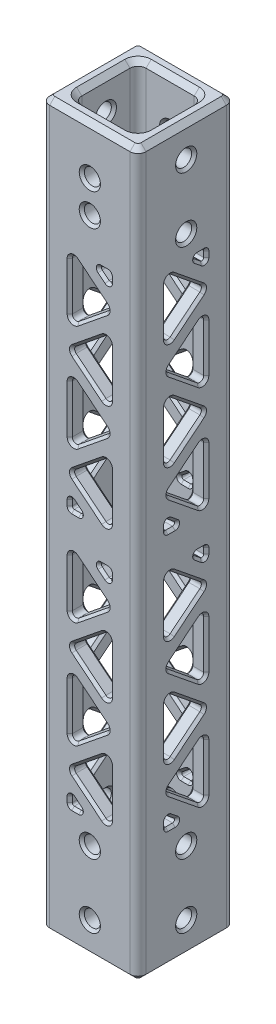
SolidWorks part; units mm, degrees
note: '?' marks a value the reader was unsure of.
ref_plane "Front Plane" through (0, 0, 0) normal (0, 0, 1) x (1, 0, 0)
ref_plane "Top Plane" through (0, 0, 0) normal (0, 1, 0) x (1, 0, 0)
ref_plane "Right Plane" through (0, 0, 0) normal (1, 0, 0) x (0, 0, -1)
sketch "Sketch1" plane through (0, 0, 0) normal (0, 1, 0) x (1, 0, 0)
  line L1 (-9.525, -9.525) -> (9.525, -9.525)
  line L2 (-9.525, -9.525) -> (-9.525, 9.525)
  line L3 (-9.525, 9.525) -> (9.525, 9.525)
  line L4 (9.525, -9.525) -> (9.525, 9.525)
  line L5 (-9.525, -9.525) -> (9.525, 9.525) construction
  line L6 (-9.525, 9.525) -> (9.525, -9.525) construction
  line L7 (-6.35, -6.35) -> (6.35, -6.35)
  line L8 (-6.35, -6.35) -> (-6.35, 6.35)
  line L9 (-6.35, 6.35) -> (6.35, 6.35)
  line L10 (6.35, -6.35) -> (6.35, 6.35)
  line L11 (-6.35, -6.35) -> (6.35, 6.35) construction
  line L12 (-6.35, 6.35) -> (6.35, -6.35) construction
  point P0 (0, 0)
  point P6 (0, 0)
  dimension "D1" = 19.05
  dimension "D2" = 19.05
  dimension "D3" = 12.7
extrude "Boss-Extrude1" add sketch "Sketch1" along normal mid plane 142.875 contours L3 L4 L1 L2
hole_wizard "1/8 (0.125) Diameter Hole1" positions "Sketch8" profile "Sketch9" hole size "1/8" standard "ANSI Inch" end condition through all
sketch "Sketch8" plane through (-9.525, 0, 0) normal (-1, 0, 0) x (0, 0, 1)
  line L2 (0, 65.0875) -> (0, 71.4375) construction
  line L3 (-9.525, 71.4375) -> (9.525, 71.4375) construction
  point P0 (0, 65.0875)
  point P2 (0, 52.3875)
  dimension "D1" = 12.7
  dimension "D2" = 6.35
sketch "Sketch9" plane through (-9.525, 65.0875, 0) normal (0, 1, 0) x (0, 0, 1)
  line L0 (0, 0) -> (0, 19.05)
  line L1 (0, 19.05) -> (1.5875, 19.05)
  line L2 (1.5875, 19.05) -> (1.5875, 0)
  line L5 (1.5875, 0) -> (0, 0)
  line L11 (0, -6.35) -> (0, 107.95) construction
  dimension "Thru Hole Dia." = 3.175
  dimension "Thru Hole Depth" = 19.05
hole_wizard "1/8 (0.125) Diameter Hole2" positions "Sketch10" profile "Sketch11" hole size "1/8" standard "ANSI Inch" end condition through all
sketch "Sketch10" plane through (9.525, 0, 0) normal (1, 0, 0) x (0, 0, -1)
  line L0 (0, -71.4375) -> (0, -65.0875) construction
  line L1 (-9.525, -71.4375) -> (9.525, -71.4375) construction
  point P0 (0, -52.3875)
  point P2 (0, -65.0875)
  dimension "D1" = 12.7
  dimension "D2" = 6.35
sketch "Sketch11" plane through (9.525, -52.3875, 0) normal (0, 1, 0) x (0, 0, -1)
  line L0 (0, 0) -> (0, 19.05)
  line L1 (0, 19.05) -> (1.5875, 19.05)
  line L2 (1.5875, 19.05) -> (1.5875, 0)
  line L5 (1.5875, 0) -> (0, 0)
  line L11 (0, -6.35) -> (0, 107.95) construction
  dimension "Thru Hole Dia." = 3.175
  dimension "Thru Hole Depth" = 19.05
hole_wizard "1/8 (0.125) Diameter Hole3" positions "Sketch15" profile "Sketch16" hole size "1/8" standard "ANSI Inch" end condition through all
sketch "Sketch15" plane through (0, 0, 9.525) normal (0, 0, 1) x (1, 0, 0)
  line L4 (0, -71.4375) -> (0, -65.0875) construction
  line L5 (-9.525, -71.4375) -> (9.525, -71.4375) construction
  line L6 (0, -65.0875) -> (0, -52.3875) construction
  line L7 (0, 55.5625) -> (0, 61.9125) construction
  line L11 (0, 61.9125) -> (0, 71.4375) construction
  line L12 (-9.525, 71.4375) -> (9.525, 71.4375) construction
  point P0 (0, 61.9125)
  point P2 (0, 55.5625)
  point P14 (0, -65.0875)
  point P16 (0, -52.3875)
  dimension "D1" = 6.35
  dimension "D2" = 9.525
  dimension "D3" = 6.35
  dimension "D4" = 12.7
sketch "Sketch16" plane through (0, 61.9125, 9.525) normal (1, 0, 0) x (0, -1, 0)
  line L0 (0, 0) -> (0, 19.05)
  line L1 (0, 19.05) -> (1.5875, 19.05)
  line L2 (1.5875, 19.05) -> (1.5875, 0)
  line L5 (1.5875, 0) -> (0, 0)
  line L11 (0, -6.35) -> (0, 107.95) construction
  dimension "Thru Hole Dia." = 3.175
  dimension "Thru Hole Depth" = 19.05
sketch "Sketch14" plane through (0, 0, 0) normal (1, 0, 0) x (0, 0, -1)
  line L0 (-3.9688, 47.625) -> (3.9688, 47.625) construction
  line L3 (3.9688, 47.625) -> (3.9688, -47.625) construction
  line L4 (-3.9688, -30.6626) -> (3.9688, -24.2253)
  line L5 (3.9688, -24.2253) -> (3.9688, -37.0998)
  line L6 (3.9688, -47.625) -> (-3.9688, -47.625) construction
  line L9 (-3.9688, -47.625) -> (-3.9688, 47.625) construction
  line L10 (0, 53.975) -> (0, 47.625) construction
  line L11 (0, -53.975) -> (0, -47.625) construction
  line L12 (-3.9687, 3.175) -> (3.9687, 3.175) construction
  line L13 (-3.9687, -3.175) -> (3.9687, -3.175) construction
  line L14 (0, -3.175) -> (0, 3.175) construction
  line L15 (-3.9688, 47.625) -> (-1.0718, 47.625)
  line L16 (-1.0718, 47.625) -> (-3.9688, 45.2756)
  line L17 (-3.9688, 45.2756) -> (-3.9688, 47.625)
  line L18 (3.9688, 47.625) -> (-3.9688, 41.1877)
  line L19 (-3.9688, 41.1877) -> (3.9688, 34.7505)
  line L20 (3.9688, 34.7505) -> (3.9688, 47.625)
  line L21 (0, 44.4064) -> (-1.9999, 46.8723) construction
  line L22 (-3.9688, 37.0998) -> (3.9688, 30.6626)
  line L23 (3.9688, 30.6626) -> (-3.9688, 24.2253)
  line L24 (-3.9688, 24.2253) -> (-3.9688, 37.0998)
  line L25 (0, 37.9691) -> (-1.9999, 35.5031) construction
  line L26 (3.9688, 26.5747) -> (-3.9688, 20.1374)
  line L27 (-3.9688, 20.1374) -> (3.9688, 13.7002)
  line L28 (3.9688, 13.7002) -> (3.9688, 26.5747)
  line L29 (-3.9687, 3.175) -> (3.9688, 9.6123)
  line L30 (3.9688, 9.6123) -> (-3.9688, 16.0495)
  line L31 (-3.9688, 16.0495) -> (-3.9687, 3.175)
  line L32 (0, 23.3561) -> (-1.9999, 25.822) construction
  line L33 (1.0718, 3.175) -> (3.9687, 3.175)
  line L34 (3.9687, 3.175) -> (3.9688, 5.5244)
  line L35 (3.9688, 5.5244) -> (1.0718, 3.175)
  line L36 (0, 16.9188) -> (-1.9999, 14.4528) construction
  line L37 (0, 6.3936) -> (1.9999, 3.9277) construction
  line L38 (-1.0718, -3.175) -> (-3.9687, -3.175)
  line L39 (-3.9687, -3.175) -> (-3.9688, -5.5244)
  line L40 (-3.9688, -5.5244) -> (-1.0718, -3.175)
  line L41 (3.9687, -3.175) -> (-3.9688, -9.6123)
  line L42 (-3.9688, -9.6123) -> (3.9688, -16.0495)
  line L43 (3.9688, -16.0495) -> (3.9687, -3.175)
  line L44 (0, -6.3936) -> (-1.9999, -3.9277) construction
  line L45 (-3.9688, -13.7002) -> (3.9688, -20.1374)
  line L46 (3.9688, -20.1374) -> (-3.9688, -26.5747)
  line L47 (-3.9688, -26.5747) -> (-3.9688, -13.7002)
  line L48 (0, -16.9188) -> (1.9999, -14.4528) construction
  line L49 (3.9688, -37.0998) -> (-3.9688, -30.6626)
  line L50 (-3.9688, -47.625) -> (3.9688, -41.1877)
  line L51 (3.9688, -41.1877) -> (-3.9688, -34.7505)
  line L52 (-3.9688, -34.7505) -> (-3.9688, -47.625)
  line L53 (0, -27.4439) -> (-1.9999, -24.978) construction
  line L54 (0, -37.9691) -> (1.9999, -35.5031) construction
  line L55 (1.0718, -47.625) -> (3.9688, -47.625)
  line L56 (3.9688, -47.625) -> (3.9688, -45.2756)
  line L57 (3.9688, -45.2756) -> (1.0718, -47.625)
  line L58 (2.5203, -46.4503) -> (0.5204, -43.9843) construction
  circle A6 centre (0, 52.3875) radius 1.5875 construction
  circle A7 centre (0, -52.3875) radius 1.5875 construction
  dimension "D3" = 3.175
  dimension "D1" = 6.35
  dimension "D2" = 7.9375
extrude "Cut-Extrude1" cut sketch "Sketch14" against normal up to next
ref_axis "Axis1" through (0, -78.5813, 0) along (0, 1, 0)?
pattern_circular "CirPattern1" count 4 over 360 about axis through (0, 0, 0) along (0, 1, 0) of "Cut-Extrude1"
fillet "Fillet1" radius 1.5875 8 edges at (9.525, 0, -9.525) (9.525, 0, 9.525) (-9.525, 0, -9.525) (-9.525, 0, 9.525) (6.35, 0, -6.35) (6.35, 0, 6.35) (-6.35, 0, 6.35) (-6.35, 0, -6.35)
fillet "Fillet2" radius 0.7937 96 edges at (-3.9688, 41.1877, -7.9375) (3.9687, 47.625, -7.9375) (3.9687, 34.7505, -7.9375) (3.9687, 30.6626, -7.9375) (-3.9688, 37.0998, -7.9375) (-3.9688, 24.2253, -7.9375) (-3.9688, 20.1374, -7.9375) (3.9687, 26.5747, -7.9375) (3.9687, 13.7002, -7.9375) (3.9687, 9.6123, -7.9375) (-3.9688, 16.0495, -7.9375) (-3.9688, 3.175, -7.9375) (-3.9688, -9.6123, -7.9375) (3.9687, -3.175, -7.9375) (3.9687, -16.0495, -7.9375) (-3.9688, -26.5747, -7.9375) (-3.9688, -13.7002, -7.9375) (3.9687, -20.1374, -7.9375) (3.9687, -24.2253, -7.9375) (-3.9688, -30.6626, -7.9375) (3.9687, -37.0998, -7.9375) (3.9687, -41.1877, -7.9375) (-3.9688, -34.7505, -7.9375) (-3.9688, -47.625, -7.9375) (-7.9375, -47.625, 3.9688) (-7.9375, -34.7505, 3.9688) (-7.9375, -41.1877, -3.9688) (-7.9375, -24.2253, -3.9688) (-7.9375, -30.6626, 3.9688) (-7.9375, -37.0998, -3.9688) (-7.9375, -26.5747, 3.9688) (-7.9375, -13.7002, 3.9688) (-7.9375, -20.1374, -3.9688) (-7.9375, -9.6123, 3.9688) (-7.9375, -3.175, -3.9687) (-7.9375, -16.0495, -3.9687) (-7.9375, 3.175, 3.9687) (-7.9375, 16.0495, 3.9688) (-7.9375, 9.6123, -3.9688) (-7.9375, 20.1374, 3.9688) (-7.9375, 26.5747, -3.9688) (-7.9375, 13.7002, -3.9688) (-7.9375, 24.2253, 3.9688) (-7.9375, 37.0998, 3.9688) (-7.9375, 30.6626, -3.9688) (-7.9375, 41.1877, 3.9687) (-7.9375, 47.625, -3.9688) (-7.9375, 34.7505, -3.9687) (-3.9687, 47.625, 7.9375) (-3.9687, 34.7505, 7.9375) (3.9688, 41.1877, 7.9375) (-3.9687, 30.6626, 7.9375) (3.9688, 24.2253, 7.9375) (3.9688, 37.0998, 7.9375) (-3.9687, 26.5747, 7.9375) (-3.9687, 13.7002, 7.9375) (3.9688, 20.1374, 7.9375) (-3.9687, 9.6123, 7.9375) (3.9688, 16.0495, 7.9375) (3.9688, 3.175, 7.9375) (-3.9687, -3.175, 7.9375) (-3.9687, -16.0495, 7.9375) (3.9688, -9.6123, 7.9375) (-3.9687, -20.1374, 7.9375) (3.9688, -13.7002, 7.9375) (3.9688, -26.5747, 7.9375) (-3.9687, -24.2253, 7.9375) (-3.9687, -37.0998, 7.9375) (3.9688, -30.6626, 7.9375) (-3.9687, -41.1877, 7.9375) (3.9688, -34.7505, 7.9375) (3.9688, -47.625, 7.9375) (7.9375, -41.1877, 3.9688) (7.9375, -34.7505, -3.9688) (7.9375, -47.625, -3.9688) (7.9375, -24.2253, 3.9688) (7.9375, -37.0998, 3.9688) (7.9375, -30.6626, -3.9688) (7.9375, -26.5747, -3.9687) (7.9375, -13.7002, -3.9688) (7.9375, -20.1374, 3.9688) (7.9375, -3.175, 3.9687) (7.9375, -16.0495, 3.9687) (7.9375, -9.6123, -3.9688) (7.9375, 3.175, -3.9687) (7.9375, 16.0495, -3.9688) (7.9375, 9.6123, 3.9688) (7.9375, 26.5747, 3.9688) (7.9375, 13.7002, 3.9688) (7.9375, 20.1374, -3.9688) (7.9375, 24.2253, -3.9688) (7.9375, 37.0998, -3.9688) (7.9375, 30.6626, 3.9688) (7.9375, 41.1877, -3.9688) (7.9375, 34.7505, 3.9687) (7.9375, 47.625, 3.9688)
fillet "Fillet3" radius 0.3969 48 edges at (1.0718, 47.625, 7.9375) (3.9688, 45.2756, 7.9375) (3.9688, 47.625, 7.9375) (-1.0718, 3.175, 7.9375) (-3.9687, 5.5244, 7.9375) (-3.9687, 3.175, 7.9375) (1.0718, -3.175, 7.9375) (3.9688, -5.5244, 7.9375) (3.9688, -3.175, 7.9375) (-1.0718, -47.625, 7.9375) (-3.9687, -45.2756, 7.9375) (-3.9687, -47.625, 7.9375) (7.9375, -47.625, 1.0718) (7.9375, -45.2756, 3.9688) (7.9375, -47.625, 3.9688) (7.9375, -3.175, -1.0718) (7.9375, -3.175, -3.9687) (7.9375, -5.5244, -3.9688) (7.9375, 3.175, 1.0718) (7.9375, 5.5244, 3.9688) (7.9375, 3.175, 3.9687) (7.9375, 47.625, -1.0718) (7.9375, 45.2756, -3.9688) (7.9375, 47.625, -3.9688) (-7.9375, 45.2756, 3.9687) (-7.9375, 47.625, 3.9688) (-7.9375, 47.625, 1.0718) (-7.9375, 3.175, -1.0718) (-7.9375, 5.5244, -3.9688) (-7.9375, 3.175, -3.9687) (-7.9375, -5.5244, 3.9688) (-7.9375, -3.175, 3.9687) (-7.9375, -3.175, 1.0718) (-7.9375, -47.625, -1.0718) (-7.9375, -45.2756, -3.9688) (-7.9375, -47.625, -3.9688) (1.0718, -47.625, -7.9375) (3.9687, -45.2756, -7.9375) (3.9687, -47.625, -7.9375) (-3.9688, -5.5244, -7.9375) (-3.9688, -3.175, -7.9375) (-1.0718, -3.175, -7.9375) (1.0718, 3.175, -7.9375) (3.9687, 5.5244, -7.9375) (3.9687, 3.175, -7.9375) (-3.9688, 45.2756, -7.9375) (-3.9688, 47.625, -7.9375) (-1.0718, 47.625, -7.9375)
chamfer "Chamfer1" distance 1.016 angle 45 32 edges at (9.525, 71.4375, 0) (9.06, 71.4375, -9.06) (9.06, 71.4375, 9.06) (0, 71.4375, -9.525) (0, 71.4375, 9.525) (-9.06, 71.4375, -9.06) (-9.06, 71.4375, 9.06) (-9.525, 71.4375, 0) (6.35, 71.4375, 0) (5.885, 71.4375, -5.885) (5.885, 71.4375, 5.885) (0, 71.4375, -6.35) (0, 71.4375, 6.35) (-5.885, 71.4375, -5.885) (-5.885, 71.4375, 5.885) (-6.35, 71.4375, 0) (0, -71.4375, 9.525) (9.06, -71.4375, 9.06) (-9.06, -71.4375, 9.06) (9.525, -71.4375, 0) (-9.525, -71.4375, 0) (9.06, -71.4375, -9.06) (-9.06, -71.4375, -9.06) (0, -71.4375, -9.525) (0, -71.4375, 6.35) (5.885, -71.4375, 5.885) (-5.885, -71.4375, 5.885) (6.35, -71.4375, 0) (-6.35, -71.4375, 0) (5.885, -71.4375, -5.885) (-5.885, -71.4375, -5.885) (0, -71.4375, -6.35)
chamfer "Chamfer2" distance 0.508 angle 45 608 edges at (2.8816, 47.625, 9.525) (2.8816, 47.625, 6.35) (2.6316, 46.36, 9.525) (2.6316, 46.36, 6.35) (3.9688, 46.6683, 9.525) (3.9688, 46.6683, 6.35) (-2.8816, 3.175, 9.525) (-2.8816, 3.175, 6.35) (-2.6316, 4.44, 9.525) (-2.6316, 4.44, 6.35) (-3.9687, 4.1317, 9.525) (-3.9687, 4.1317, 6.35) (2.8816, -3.175, 9.525) (2.8816, -3.175, 6.35) (2.6316, -4.44, 9.525) (2.6316, -4.44, 6.35) (3.9688, -4.1317, 9.525) (3.9688, -4.1317, 6.35) (-2.8816, -47.625, 9.525) (-2.8816, -47.625, 6.35) (-2.6316, -46.36, 9.525) (-2.6316, -46.36, 6.35) (-3.9687, -46.6683, 9.525) (-3.9687, -46.6683, 6.35) (9.525, -47.625, 2.8816) (6.35, -47.625, 2.8816) (9.525, -46.36, 2.6316) (6.35, -46.36, 2.6316) (9.525, -46.6683, 3.9688) (6.35, -46.6683, 3.9688) (9.525, -3.175, -2.8816) (6.35, -3.175, -2.8816) (9.525, -4.44, -2.6316) (6.35, -4.44, -2.6316) (9.525, -4.1317, -3.9687) (6.35, -4.1317, -3.9687) (9.525, 3.175, 2.8816) (6.35, 3.175, 2.8816) (9.525, 4.44, 2.6316) (6.35, 4.44, 2.6316) (9.525, 4.1317, 3.9687) (6.35, 4.1317, 3.9687) (9.525, 47.625, -2.8816) (6.35, 47.625, -2.8816) (9.525, 46.36, -2.6316) (6.35, 46.36, -2.6316) (9.525, 46.6683, -3.9688) (6.35, 46.6683, -3.9688) (-9.525, 46.36, 2.6316) (-6.35, 46.36, 2.6316) (-9.525, 46.6683, 3.9688) (-6.35, 46.6683, 3.9688) (-9.525, 47.625, 2.8816) (-6.35, 47.625, 2.8816) (-9.525, 3.175, -2.8816) (-6.35, 3.175, -2.8816) (-9.525, 4.44, -2.6316) (-6.35, 4.44, -2.6316) (-9.525, 4.1317, -3.9687) (-6.35, 4.1317, -3.9687) (-9.525, -4.44, 2.6316) (-6.35, -4.44, 2.6316) (-9.525, -4.1317, 3.9687) (-6.35, -4.1317, 3.9687) (-9.525, -3.175, 2.8816) (-6.35, -3.175, 2.8816) (-9.525, -47.625, -2.8816) (-6.35, -47.625, -2.8816) (-9.525, -46.36, -2.6316) (-6.35, -46.36, -2.6316) (-9.525, -46.6683, -3.9688) (-6.35, -46.6683, -3.9688) (2.8816, -47.625, -9.525) (2.8816, -47.625, -6.35) (2.6316, -46.36, -9.525) (2.6316, -46.36, -6.35) (3.9687, -46.6683, -9.525) (3.9687, -46.6683, -6.35) (-2.6316, -4.44, -9.525) (-2.6316, -4.44, -6.35) (-3.9688, -4.1317, -9.525) (-3.9688, -4.1317, -6.35) (-2.8816, -3.175, -9.525) (-2.8816, -3.175, -6.35) (2.8816, 3.175, -9.525) (2.8816, 3.175, -6.35) (2.6316, 4.44, -9.525) (2.6316, 4.44, -6.35) (3.9687, 4.1317, -9.525) (3.9687, 4.1317, -6.35) (-2.6316, 46.36, -9.525) (-2.6316, 46.36, -6.35) (-3.9688, 46.6683, -9.525) (-3.9688, 46.6683, -6.35) (-2.8816, 47.625, -9.525) (-2.8816, 47.625, -6.35) (1.8172, 47.3607, 6.35) (1.8172, 47.3607, 9.525) (3.7426, 45.7502, 6.35) (3.7426, 45.7502, 9.525) (3.8525, 47.5088, 6.35) (3.8525, 47.5088, 9.525) (-1.8172, 3.4393, 6.35) (-1.8172, 3.4393, 9.525) (-3.7426, 5.0498, 6.35) (-3.7426, 5.0498, 9.525) (-3.8525, 3.2912, 6.35) (-3.8525, 3.2912, 9.525) (1.8172, -3.4393, 6.35) (1.8172, -3.4393, 9.525) (3.7426, -5.0498, 6.35) (3.7426, -5.0498, 9.525) (3.8525, -3.2912, 6.35) (3.8525, -3.2912, 9.525) (-1.8172, -47.3607, 6.35) (-1.8172, -47.3607, 9.525) (-3.7426, -45.7502, 6.35) (-3.7426, -45.7502, 9.525) (-3.8525, -47.5088, 6.35) (-3.8525, -47.5088, 9.525) (6.35, -47.3607, 1.8172) (9.525, -47.3607, 1.8172) (6.35, -45.7502, 3.7426) (9.525, -45.7502, 3.7426) (6.35, -47.5088, 3.8525) (9.525, -47.5088, 3.8525) (6.35, -3.4393, -1.8172) (9.525, -3.4393, -1.8172) (6.35, -3.2912, -3.8525) (9.525, -3.2912, -3.8525) (6.35, -5.0498, -3.7426) (9.525, -5.0498, -3.7426) (6.35, 3.4393, 1.8172) (9.525, 3.4393, 1.8172) (6.35, 5.0498, 3.7426) (9.525, 5.0498, 3.7426) (6.35, 3.2912, 3.8525) (9.525, 3.2912, 3.8525) (6.35, 47.3607, -1.8172) (9.525, 47.3607, -1.8172) (6.35, 45.7502, -3.7426) (9.525, 45.7502, -3.7426) (6.35, 47.5088, -3.8525) (9.525, 47.5088, -3.8525) (-6.35, 45.7502, 3.7426) (-9.525, 45.7502, 3.7426) (-6.35, 47.5088, 3.8525) (-9.525, 47.5088, 3.8525) (-6.35, 47.3607, 1.8172) (-9.525, 47.3607, 1.8172) (-6.35, 3.4393, -1.8172) (-9.525, 3.4393, -1.8172) (-6.35, 5.0498, -3.7426) (-9.525, 5.0498, -3.7426) (-6.35, 3.2912, -3.8525) (-9.525, 3.2912, -3.8525) (-6.35, -5.0498, 3.7426) (-9.525, -5.0498, 3.7426) (-6.35, -3.2912, 3.8525) (-9.525, -3.2912, 3.8525) (-6.35, -3.4393, 1.8172) (-9.525, -3.4393, 1.8172) (-6.35, -47.3607, -1.8172) (-9.525, -47.3607, -1.8172) (-6.35, -45.7502, -3.7426) (-9.525, -45.7502, -3.7426) (-6.35, -47.5088, -3.8525) (-9.525, -47.5088, -3.8525) (1.8172, -47.3607, -6.35) (1.8172, -47.3607, -9.525) (3.7426, -45.7502, -6.35) (3.7426, -45.7502, -9.525) (3.8525, -47.5088, -6.35) (3.8525, -47.5088, -9.525) (-3.7426, -5.0498, -6.35) (-3.7426, -5.0498, -9.525) (-3.8525, -3.2912, -6.35) (-3.8525, -3.2912, -9.525) (-1.8172, -3.4393, -6.35) (-1.8172, -3.4393, -9.525) (1.8172, 3.4393, -6.35) (1.8172, 3.4393, -9.525) (3.7426, 5.0498, -6.35) (3.7426, 5.0498, -9.525) (3.8525, 3.2912, -6.35) (3.8525, 3.2912, -9.525) (-3.7426, 45.7502, -6.35) (-3.7426, 45.7502, -9.525) (-3.8525, 47.5088, -6.35) (-3.8525, 47.5088, -9.525) (-1.8172, 47.3607, -6.35) (-1.8172, 47.3607, -9.525) (6.35, 52.3875, 1.5875) (-6.35, 52.3875, -1.5875) (-9.525, 52.3875, 1.5875) (9.525, 52.3875, 1.5875) (-6.35, 65.0875, -1.5875) (6.35, 65.0875, 1.5875) (9.525, 65.0875, 1.5875) (-9.525, 65.0875, 1.5875) (6.35, -65.0875, 1.5875) (-6.35, -65.0875, -1.5875) (-9.525, -65.0875, -1.5875) (9.525, -65.0875, -1.5875) (6.35, -52.3875, 1.5875) (-6.35, -52.3875, -1.5875) (-9.525, -52.3875, -1.5875) (9.525, -52.3875, -1.5875) (-0.2668, 38.1854, -9.525) (-0.2668, 38.1854, -6.35) (-0.2668, 44.19, -9.525) (-0.2668, 44.19, -6.35) (3.9687, 41.1877, -9.525) (3.9687, 41.1877, -6.35) (0.2668, 33.6649, -9.525) (0.2668, 33.6649, -6.35) (0.2668, 27.6603, -9.525) (0.2668, 27.6603, -6.35) (-3.9688, 30.6626, -9.525) (-3.9688, 30.6626, -6.35) (-0.2668, 17.1351, -9.525) (-0.2668, 17.1351, -6.35) (-0.2668, 23.1397, -9.525) (-0.2668, 23.1397, -6.35) (3.9687, 20.1374, -9.525) (3.9687, 20.1374, -6.35) (0.2668, 12.6146, -9.525) (0.2668, 12.6146, -6.35) (0.2668, 6.61, -9.525) (0.2668, 6.61, -6.35) (-3.9688, 9.6123, -9.525) (-3.9688, 9.6123, -6.35) (-0.2668, -12.6146, -9.525) (-0.2668, -12.6146, -6.35) (-0.2668, -6.61, -9.525) (-0.2668, -6.61, -6.35) (3.9687, -9.6123, -9.525) (3.9687, -9.6123, -6.35) (0.2668, -23.1397, -9.525) (0.2668, -23.1397, -6.35) (-3.9688, -20.1374, -9.525) (-3.9688, -20.1374, -6.35) (0.2668, -17.1351, -9.525) (0.2668, -17.1351, -6.35) (-0.2668, -27.6603, -9.525) (-0.2668, -27.6603, -6.35) (3.9687, -30.6626, -9.525) (3.9687, -30.6626, -6.35) (-0.2668, -33.6649, -9.525) (-0.2668, -33.6649, -6.35) (0.2668, -38.1854, -9.525) (0.2668, -38.1854, -6.35) (0.2668, -44.19, -9.525) (0.2668, -44.19, -6.35) (-3.9688, -41.1877, -9.525) (-3.9688, -41.1877, -6.35) (-9.525, -44.19, -0.2668) (-6.35, -44.19, -0.2668) (-9.525, -41.1877, 3.9688) (-6.35, -41.1877, 3.9688) (-9.525, -38.1854, -0.2668) (-6.35, -38.1854, -0.2668) (-9.525, -27.6603, 0.2668) (-6.35, -27.6603, 0.2668) (-9.525, -30.6626, -3.9688) (-6.35, -30.6626, -3.9688) (-9.525, -33.6649, 0.2668) (-6.35, -33.6649, 0.2668) (-9.525, -23.1397, -0.2668) (-6.35, -23.1397, -0.2668) (-9.525, -20.1374, 3.9688) (-6.35, -20.1374, 3.9688) (-9.525, -17.1351, -0.2668) (-6.35, -17.1351, -0.2668) (1.5875, -52.3875, -6.35) (-1.5875, -52.3875, 6.35) (-9.525, -12.6146, 0.2668) (-6.35, -12.6146, 0.2668) (1.5875, -52.3875, 9.525) (1.5875, -52.3875, -9.525) (-9.525, -6.61, 0.2668) (-6.35, -6.61, 0.2668) (-9.525, -9.6123, -3.9687) (-6.35, -9.6123, -3.9687) (-9.525, 6.61, -0.2668) (-6.35, 6.61, -0.2668) (-9.525, 9.6123, 3.9687) (-6.35, 9.6123, 3.9687) (-9.525, 12.6146, -0.2668) (-6.35, 12.6146, -0.2668) (-9.525, 17.1351, 0.2668) (-6.35, 17.1351, 0.2668) (-9.525, 23.1397, 0.2668) (-6.35, 23.1397, 0.2668) (-9.525, 20.1374, -3.9688) (-6.35, 20.1374, -3.9688) (-9.525, 27.6603, -0.2668) (-6.35, 27.6603, -0.2668) (-9.525, 30.6626, 3.9688) (-6.35, 30.6626, 3.9688) (-9.525, 33.6649, -0.2668) (-6.35, 33.6649, -0.2668) (-9.525, 38.1854, 0.2668) (-6.35, 38.1854, 0.2668) (-9.525, 44.19, 0.2668) (-6.35, 44.19, 0.2668) (-9.525, 41.1877, -3.9688) (-6.35, 41.1877, -3.9688) (0.2668, 44.19, 9.525) (0.2668, 44.19, 6.35) (-3.9687, 41.1877, 9.525) (-3.9687, 41.1877, 6.35) (0.2668, 38.1854, 9.525) (0.2668, 38.1854, 6.35) (-0.2668, 33.6649, 9.525) (-0.2668, 33.6649, 6.35) (-0.2668, 27.6603, 9.525) (-0.2668, 27.6603, 6.35) (3.9688, 30.6626, 9.525) (3.9688, 30.6626, 6.35) (0.2668, 23.1397, 9.525) (0.2668, 23.1397, 6.35) (-3.9687, 20.1374, 9.525) (-3.9687, 20.1374, 6.35) (0.2668, 17.1351, 9.525) (0.2668, 17.1351, 6.35) (-0.2668, 12.6146, 9.525) (-0.2668, 12.6146, 6.35) (-0.2668, 6.61, 9.525) (-0.2668, 6.61, 6.35) (3.9688, 9.6123, 9.525) (3.9688, 9.6123, 6.35) (0.2668, -6.61, 9.525) (0.2668, -6.61, 6.35) (-3.9687, -9.6123, 9.525) (-3.9687, -9.6123, 6.35) (0.2668, -12.6146, 9.525) (0.2668, -12.6146, 6.35) (-0.2668, -17.1351, 9.525) (-0.2668, -17.1351, 6.35) (-0.2668, -23.1397, 9.525) (-0.2668, -23.1397, 6.35) (3.9688, -20.1374, 9.525) (3.9688, -20.1374, 6.35) (0.2668, -27.6603, 9.525) (0.2668, -27.6603, 6.35) (-3.9687, -30.6626, 9.525) (-3.9687, -30.6626, 6.35) (0.2668, -33.6649, 9.525) (0.2668, -33.6649, 6.35) (-0.2668, -38.1854, 9.525) (-0.2668, -38.1854, 6.35) (-0.2668, -44.19, 9.525) (-0.2668, -44.19, 6.35) (3.9688, -41.1877, 9.525) (3.9688, -41.1877, 6.35) (1.5875, -65.0875, -6.35) (-1.5875, -65.0875, 6.35) (9.525, -38.1854, 0.2668) (6.35, -38.1854, 0.2668) (1.5875, -65.0875, 9.525) (1.5875, -65.0875, -9.525) (9.525, -44.19, 0.2668) (6.35, -44.19, 0.2668) (9.525, -41.1877, -3.9688) (6.35, -41.1877, -3.9688) (9.525, -27.6603, -0.2668) (6.35, -27.6603, -0.2668) (9.525, -30.6626, 3.9688) (6.35, -30.6626, 3.9688) (9.525, -33.6649, -0.2668) (6.35, -33.6649, -0.2668) (9.525, -23.1397, 0.2668) (6.35, -23.1397, 0.2668) (9.525, -20.1374, -3.9688) (6.35, -20.1374, -3.9688) (9.525, -17.1351, 0.2668) (6.35, -17.1351, 0.2668) (9.525, -6.61, -0.2668) (6.35, -6.61, -0.2668) (9.525, -9.6123, 3.9687) (6.35, -9.6123, 3.9687) (9.525, -12.6146, -0.2668) (6.35, -12.6146, -0.2668) (9.525, 6.61, 0.2668) (6.35, 6.61, 0.2668) (9.525, 9.6123, -3.9687) (6.35, 9.6123, -3.9687) (9.525, 12.6146, 0.2668) (6.35, 12.6146, 0.2668) (9.525, 23.1397, -0.2668) (6.35, 23.1397, -0.2668) (9.525, 20.1374, 3.9688) (6.35, 20.1374, 3.9688) (9.525, 17.1351, -0.2668) (6.35, 17.1351, -0.2668) (9.525, 27.6603, 0.2668) (6.35, 27.6603, 0.2668) (9.525, 30.6626, -3.9688) (6.35, 30.6626, -3.9688) (9.525, 33.6649, 0.2668) (6.35, 33.6649, 0.2668) (9.525, 38.1854, -0.2668) (6.35, 38.1854, -0.2668) (9.525, 44.19, -0.2668) (6.35, 44.19, -0.2668) (9.525, 41.1877, 3.9688) (6.35, 41.1877, 3.9688) (-3.5024, 41.1877, -6.35) (-3.5024, 41.1877, -9.525) (3.5165, 46.6759, -6.35) (3.5165, 46.6759, -9.525) (3.5165, 35.6996, -6.35) (3.5165, 35.6996, -9.525) (3.5024, 30.6626, -6.35) (3.5024, 30.6626, -9.525) (-3.5165, 36.1507, -6.35) (-3.5165, 36.1507, -9.525) (-3.5165, 25.1745, -6.35) (-3.5165, 25.1745, -9.525) (-3.5024, 20.1374, -6.35) (-3.5024, 20.1374, -9.525) (3.5165, 25.6255, -6.35) (3.5165, 25.6255, -9.525) (3.5165, 14.6493, -6.35) (3.5165, 14.6493, -9.525) (3.5024, 9.6123, -6.35) (3.5024, 9.6123, -9.525) (-3.5165, 15.1004, -6.35) (-3.5165, 15.1004, -9.525) (-3.5165, 4.1241, -6.35) (-3.5165, 4.1241, -9.525) (-3.5024, -9.6123, -6.35) (-3.5024, -9.6123, -9.525) (3.5165, -4.1241, -6.35) (3.5165, -4.1241, -9.525) (3.5165, -15.1004, -6.35) (3.5165, -15.1004, -9.525) (-3.5165, -25.6255, -6.35) (-3.5165, -25.6255, -9.525) (-3.5165, -14.6493, -6.35) (-3.5165, -14.6493, -9.525) (3.5024, -20.1374, -6.35) (3.5024, -20.1374, -9.525) (3.5165, -25.1745, -6.35) (3.5165, -25.1745, -9.525) (-3.5024, -30.6626, -6.35) (-3.5024, -30.6626, -9.525) (3.5165, -36.1507, -6.35) (3.5165, -36.1507, -9.525) (3.5024, -41.1877, -6.35) (3.5024, -41.1877, -9.525) (-3.5165, -35.6996, -6.35) (-3.5165, -35.6996, -9.525) (-3.5165, -46.6759, -6.35) (-3.5165, -46.6759, -9.525) (-6.35, -46.6759, 3.5165) (-9.525, -46.6759, 3.5165) (-6.35, -35.6996, 3.5165) (-9.525, -35.6996, 3.5165) (-6.35, -41.1877, -3.5024) (-9.525, -41.1877, -3.5024) (-6.35, -25.1745, -3.5165) (-9.525, -25.1745, -3.5165) (-6.35, -30.6626, 3.5024) (-9.525, -30.6626, 3.5024) (-6.35, -36.1507, -3.5165) (-9.525, -36.1507, -3.5165) (-6.35, -25.6255, 3.5165) (-9.525, -25.6255, 3.5165) (-6.35, -14.6493, 3.5165) (-9.525, -14.6493, 3.5165) (-6.35, -20.1374, -3.5024) (-9.525, -20.1374, -3.5024) (-6.35, -9.6123, 3.5024) (-9.525, -9.6123, 3.5024) (-6.35, -4.1241, -3.5165) (-9.525, -4.1241, -3.5165) (-6.35, -15.1004, -3.5165) (-9.525, -15.1004, -3.5165) (-6.35, 4.1241, 3.5165) (-9.525, 4.1241, 3.5165) (-6.35, 15.1004, 3.5165) (-9.525, 15.1004, 3.5165) (-6.35, 9.6123, -3.5024) (-9.525, 9.6123, -3.5024) (-6.35, 20.1374, 3.5024) (-9.525, 20.1374, 3.5024) (-6.35, 25.6255, -3.5165) (1.5875, 55.5625, -6.35) (-9.525, 25.6255, -3.5165) (-6.35, 14.6493, -3.5165) (-9.525, 14.6493, -3.5165) (-1.5875, 55.5625, 6.35) (-6.35, 25.1745, 3.5165) (-9.525, 25.1745, 3.5165) (1.5875, 55.5625, 9.525) (-6.35, 36.1507, 3.5165) (-9.525, 36.1507, 3.5165) (-6.35, 30.6626, -3.5024) (1.5875, 55.5625, -9.525) (-9.525, 30.6626, -3.5024) (-6.35, 41.1877, 3.5024) (-9.525, 41.1877, 3.5024) (-6.35, 46.6759, -3.5165) (-9.525, 46.6759, -3.5165) (-6.35, 35.6996, -3.5165) (-9.525, 35.6996, -3.5165) (-3.5165, 46.6759, 6.35) (-3.5165, 46.6759, 9.525) (-3.5165, 35.6996, 6.35) (-3.5165, 35.6996, 9.525) (3.5024, 41.1877, 6.35) (3.5024, 41.1877, 9.525) (-3.5024, 30.6626, 6.35) (-3.5024, 30.6626, 9.525) (3.5165, 25.1745, 6.35) (3.5165, 25.1745, 9.525) (3.5165, 36.1507, 6.35) (3.5165, 36.1507, 9.525) (-3.5165, 25.6255, 6.35) (-3.5165, 25.6255, 9.525) (-3.5165, 14.6493, 6.35) (-3.5165, 14.6493, 9.525) (3.5024, 20.1374, 6.35) (3.5024, 20.1374, 9.525) (-3.5024, 9.6123, 6.35) (-3.5024, 9.6123, 9.525) (3.5165, 15.1004, 6.35) (3.5165, 15.1004, 9.525) (3.5165, 4.1241, 6.35) (3.5165, 4.1241, 9.525) (-3.5165, -4.1241, 6.35) (-3.5165, -4.1241, 9.525) (-3.5165, -15.1004, 6.35) (-3.5165, -15.1004, 9.525) (3.5024, -9.6123, 6.35) (3.5024, -9.6123, 9.525) (-3.5024, -20.1374, 6.35) (-3.5024, -20.1374, 9.525) (3.5165, -14.6493, 6.35) (3.5165, -14.6493, 9.525) (3.5165, -25.6255, 6.35) (3.5165, -25.6255, 9.525) (-3.5165, -25.1745, 6.35) (-3.5165, -25.1745, 9.525) (-3.5165, -36.1507, 6.35) (-3.5165, -36.1507, 9.525) (3.5024, -30.6626, 6.35) (3.5024, -30.6626, 9.525) (-3.5024, -41.1877, 6.35) (-3.5024, -41.1877, 9.525) (3.5165, -35.6996, 6.35) (3.5165, -35.6996, 9.525) (3.5165, -46.6759, 6.35) (3.5165, -46.6759, 9.525) (6.35, -41.1877, 3.5024) (9.525, -41.1877, 3.5024) (6.35, -35.6996, -3.5165) (9.525, -35.6996, -3.5165) (6.35, -46.6759, -3.5165) (9.525, -46.6759, -3.5165) (6.35, -25.1745, 3.5165) (9.525, -25.1745, 3.5165) (6.35, -36.1507, 3.5165) (9.525, -36.1507, 3.5165) (6.35, -30.6626, -3.5024) (9.525, -30.6626, -3.5024) (6.35, -25.6255, -3.5165) (9.525, -25.6255, -3.5165) (6.35, -14.6493, -3.5165) (9.525, -14.6493, -3.5165) (6.35, -20.1374, 3.5024) (9.525, -20.1374, 3.5024) (6.35, -4.1241, 3.5165) (9.525, -4.1241, 3.5165) (6.35, -15.1004, 3.5165) (9.525, -15.1004, 3.5165) (6.35, -9.6123, -3.5024) (9.525, -9.6123, -3.5024) (6.35, 4.1241, -3.5165) (9.525, 4.1241, -3.5165) (6.35, 15.1004, -3.5165) (9.525, 15.1004, -3.5165) (6.35, 9.6123, 3.5024) (9.525, 9.6123, 3.5024) (6.35, 25.6255, 3.5165) (9.525, 25.6255, 3.5165) (6.35, 14.6493, 3.5165) (9.525, 14.6493, 3.5165) (6.35, 20.1374, -3.5024) (9.525, 20.1374, -3.5024) (6.35, 25.1745, -3.5165) (9.525, 25.1745, -3.5165) (6.35, 36.1507, -3.5165) (9.525, 36.1507, -3.5165) (6.35, 30.6626, 3.5024) (9.525, 30.6626, 3.5024) (6.35, 41.1877, -3.5024) (9.525, 41.1877, -3.5024) (6.35, 35.6996, 3.5165) (9.525, 35.6996, 3.5165) (6.35, 46.6759, 3.5165) (9.525, 46.6759, 3.5165) (-1.5875, 61.9125, 6.35) (1.5875, 61.9125, -6.35) (1.5875, 61.9125, -9.525) (1.5875, 61.9125, 9.525)
equation "\"D2@Sketch1\"=\"D1@Sketch1\""
